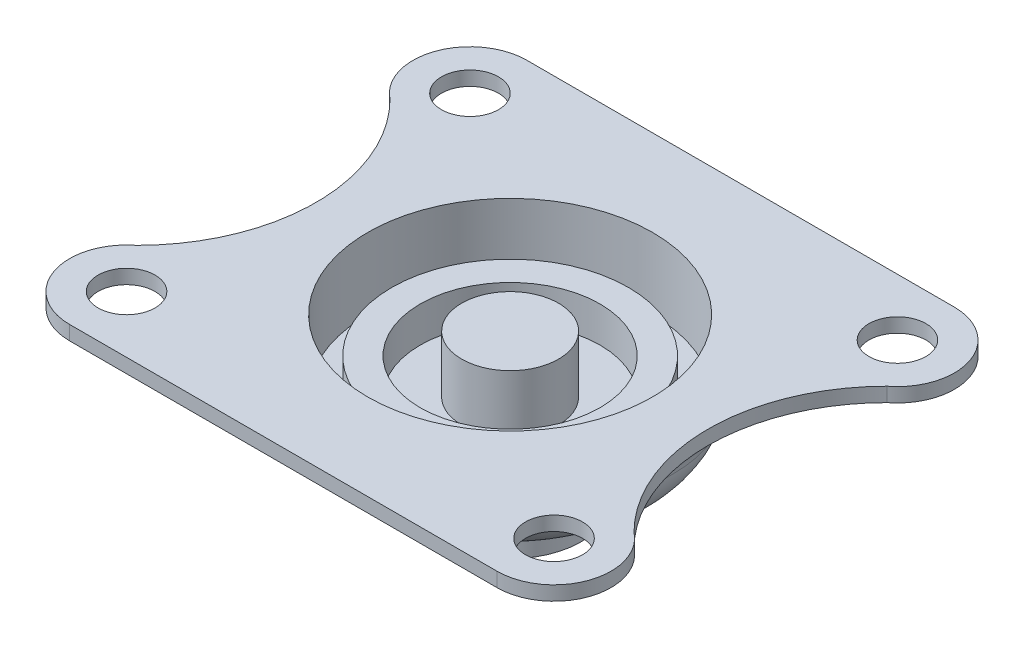
SolidWorks part; units mm, degrees
other "Markup1"
sketch "Sketch14" plane through (-18.13, -10.3, -16.05) normal (-0.0213, -0.9995, -0.0237) x (0.9838, -0.0252, 0.1773)
ref_plane "Front Plane" through (0, 0, 0) normal (0, 0, 1) x (1, 0, 0)
ref_plane "Top Plane" through (0, 0, 0) normal (0, 1, 0) x (1, 0, 0)
ref_plane "Right Plane" through (0, 0, 0) normal (1, 0, 0) x (0, 0, -1)
sketch "Sketch1" plane through (0, 0, 0) normal (0, 1, 0) x (1, 0, 0)
  line L0 (0.87, 0) -> (0.87, 13.6957) construction
  line L1 (-14.13, 16.05) -> (15.87, 16.05)
  line L5 (-14.13, -16.05) -> (15.87, -16.05)
  line L6 (0.87, 0) -> (-7.5142, 0) construction
  arc A0 (-14.13, 16.05) -> (-16.5707, 8.8809) centre (-14.13, 12.05) ccw
  arc A3 (15.87, 16.05) -> (18.3108, 8.8809) centre (15.87, 12.05) cw
  circle A6 centre (-14.13, 12.05) radius 2
  arc A7 (15.87, -16.05) -> (18.3108, -8.8809) centre (15.87, -12.05) ccw
  circle A8 centre (-14.13, -12.05) radius 2
  arc A9 (-14.13, -16.05) -> (-16.5707, -8.8809) centre (-14.13, -12.05) cw
  arc A10 (-16.5707, 8.8809) -> (-16.5707, -8.8809) centre (-25.4516, 0) cw
  circle A11 centre (15.87, -12.05) radius 2
  circle A12 centre (15.87, 12.05) radius 2
  arc A13 (18.3108, 8.8809) -> (18.3108, -8.8809) centre (27.1917, 0) ccw
  point P0 (0, 0)
  dimension "D2" = 8
  dimension "D1" = 4
extrude "Boss-Extrude2" add sketch "Sketch1" along normal blind 1
sketch "Sketch3" plane through (0, 0, 0) normal (0, -1, 0) x (1, 0, 0)
  circle A0 centre (0.7385, 0) radius 11
  dimension "D1" = 22
extrude "Boss-Extrude4" add sketch "Sketch3" along normal blind 5
sketch "Sketch6" plane through (0, 1, 0) normal (0, 1, 0) x (1, 0, 0)
  circle A2 centre (0.7385, 0) radius 10
  circle A3 centre (0.7385, 0) radius 10
  dimension "D1" = 1
extrude "Cut-Extrude2" cut sketch "Sketch6" against normal blind 5
sketch "Sketch7" plane through (0, -4, 0) normal (0, 1, 0) x (1, 0, 0)
  circle A2 centre (0.7385, 0) radius 3.4
  circle A3 centre (0.7385, 0) radius 6.3092
  circle A4 centre (0.7385, 0) radius 8.3092
  dimension "D1" = 6.8
  dimension "D2" = 2
extrude "Boss-Extrude5" add sketch "Sketch7" along normal blind 2.5 contours A4 A3 region at (-7.3357, -4, 0)
extrude "Boss-Extrude6" add sketch "Sketch7<3>" along normal blind 4 contours A2
sketch "Sketch7<3>" plane through (0, -4, 0) normal (0, 1, 0) x (1, 0, 0) same geometry as "Sketch7"
sketch "Sketch8" plane through (0, -5, 0) normal (0, -1, 0) x (1, 0, 0)
  circle A1 centre (0.7385, 0) radius 5
  circle A2 centre (0.7385, 0) radius 8
  circle A3 centre (0.7385, 0) radius 8
  dimension "D1" = 3
  dimension "D2" = 3
sketch "Sketch10" plane through (0, -5, 0) normal (0, -1, 0) x (1, 0, 0)
  circle A0 centre (0.7385, 0) radius 11 construction
  circle A1 centre (0.7385, 0) radius 11
extrude "Boss-Extrude7" add sketch "Sketch10" along normal blind 2
sketch "Sketch11" plane through (0, -7, 0) normal (0, -1, 0) x (1, 0, 0)
  circle A1 centre (0.7385, 0) radius 8
  circle A2 centre (0.7385, 0) radius 8
  circle A3 centre (0.7385, 0) radius 5
  circle A4 centre (0.7385, 0) radius 5
  dimension "D1" = 0
  dimension "D2" = 0
extrude "Cut-Extrude5" cut sketch "Sketch11" against normal blind 2
sketch "Sketch12" plane through (0, -7, 0) normal (0, -1, 0) x (1, 0, 0)
  circle A1 centre (0.7385, 0) radius 5 construction
  circle A3 centre (0.7385, 0) radius 2
  dimension "D1" = 4
extrude "Boss-Extrude9" add sketch "Sketch12" along normal blind 1.3
sketch "Sketch13" plane through (0, -8.3, 0) normal (0, -1, 0) x (1, 0, 0)
  circle A3 centre (0.7385, 0) radius 5
  dimension "D1" = 10
extrude "Boss-Extrude10" add sketch "Sketch13" along normal blind 2
fillet "Fillet1" radius 5 1 edges at (0.7385, -7, -11)
fillet "Fillet2" radius 5 1 edges at (0.7385, 0, 11)
fillet "Fillet3" radius 2 1 edges at (0.7385, -5, -5)
